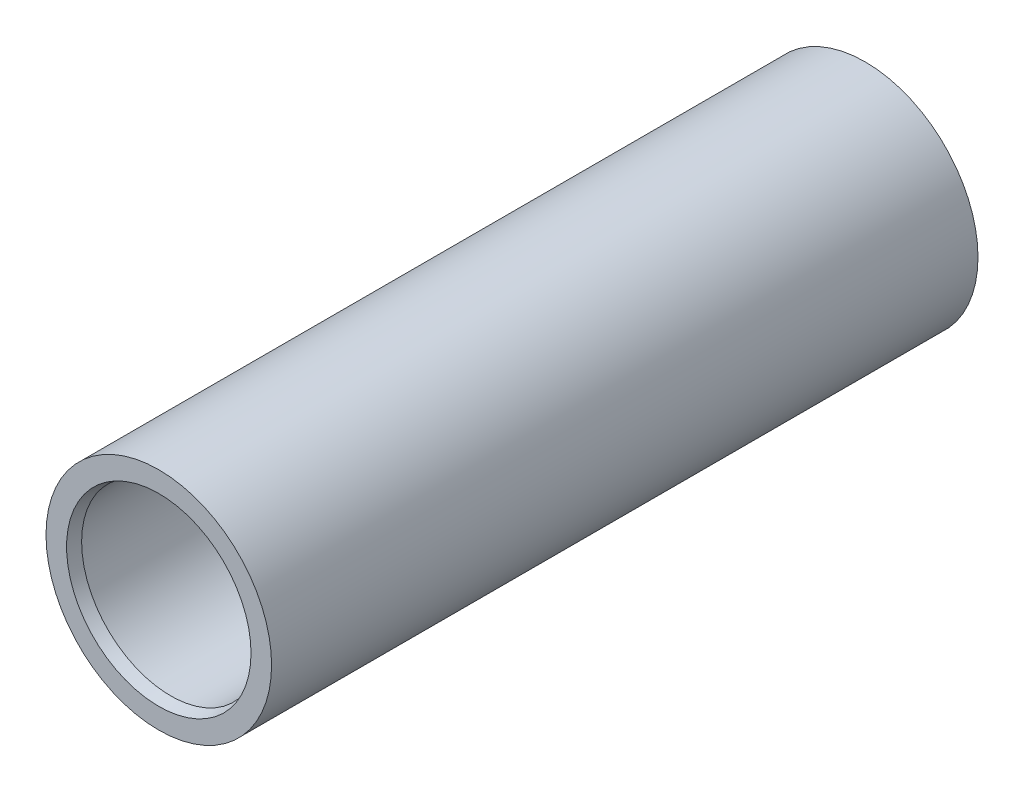
SolidWorks part; units mm, degrees
material "Plain Carbon Steel"
ref_plane "Front" through (0, 0, 0) normal (0, 0, 1) x (1, 0, 0)
ref_plane "Top" through (0, 0, 0) normal (0, 1, 0) x (1, 0, 0)
ref_plane "Right" through (0, 0, 0) normal (1, 0, 0) x (0, 0, -1)
ref_axis "Axis1" through (-84.4107, 0, 0) along (1, 0, 0)
ref_axis "Axis2" through (0, 64.3378, 0) along (0, -1, 0)
ref_axis "Axis3" through (0, 0, -102.329) along (0, 0, 1)
sketch "Sketch1" plane through (0, 0, 0) normal (0, 0, 1) x (1, 0, 0)
  circle A0 centre (0, 0) radius 38
  circle A1 centre (0, 0) radius 30
  dimension "D1" = 76
  dimension "D2" = 60
extrude "Boss-Extrude1" add sketch "Sketch1" along normal blind 238
chamfer "Chamfer1" distance 4 angle 15 1 edges at (30, 0, 0) first distance on face at (30, 0, 238)
chamfer "Chamfer2" distance 4 angle 15 1 edges at (30, 0, 238) first distance on face at (30, 0, 4)
